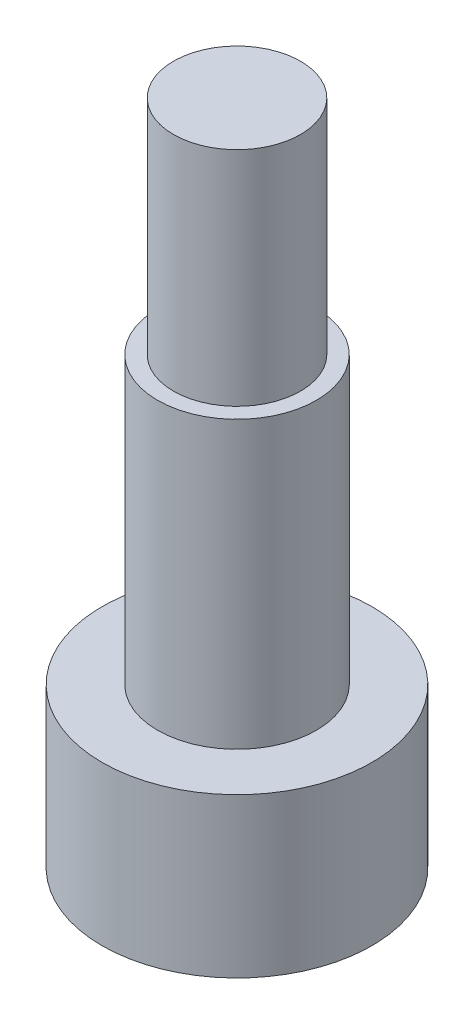
SolidWorks part; units mm, degrees
ref_plane "Front Plane" through (0, 0, 0) normal (0, 0, 1) x (1, 0, 0)
ref_plane "Top Plane" through (0, 0, 0) normal (0, 1, 0) x (1, 0, 0)
ref_plane "Right Plane" through (0, 0, 0) normal (1, 0, 0) x (0, 0, -1)
sketch "Sketch1" plane through (0, 0, 0) normal (0, 0, 1) x (1, 0, 0)
  line L0 (0, 0) -> (4.25, 0)
  line L1 (4.675, 0) -> (-4.675, 0) construction
  line L2 (4.25, 0) -> (4.25, 5)
  line L3 (4.25, 5) -> (2.5, 5)
  line L4 (2.5, 5) -> (2.5, 14)
  line L5 (2.5, 14) -> (2, 14)
  line L6 (0, -4.675) -> (0, 4.675) construction
  line L7 (0, 21) -> (0, 0)
  line L8 (2, 14) -> (2, 21)
  line L9 (2, 21) -> (0, 21)
  dimension "D1" = 5
  dimension "D2" = 4.25
  dimension "D3" = 2.5
  dimension "D4" = 2
  dimension "D5" = 16
  dimension "D6" = 7
revolve "Revolve1" add sketch "Sketch1" angle 360 about L7
sketch "Sketch2" plane through (0, 0, 0) normal (0, -1, 0) x (1, 0, 0)
  line L1 (0, -1.7321) -> (1.5, -0.866)
  line L2 (1.5, -0.866) -> (1.5, 0.866)
  line L3 (1.5, 0.866) -> (0, 1.7321)
  line L4 (0, 1.7321) -> (-1.5, 0.866)
  line L5 (-1.5, 0.866) -> (-1.5, -0.866)
  line L6 (-1.5, -0.866) -> (0, -1.7321)
  circle A0 centre (0, 0) radius 1.5 construction
  dimension "D1" = 3
extrude "Cut-Extrude1" cut sketch "Sketch2" against normal blind 2
